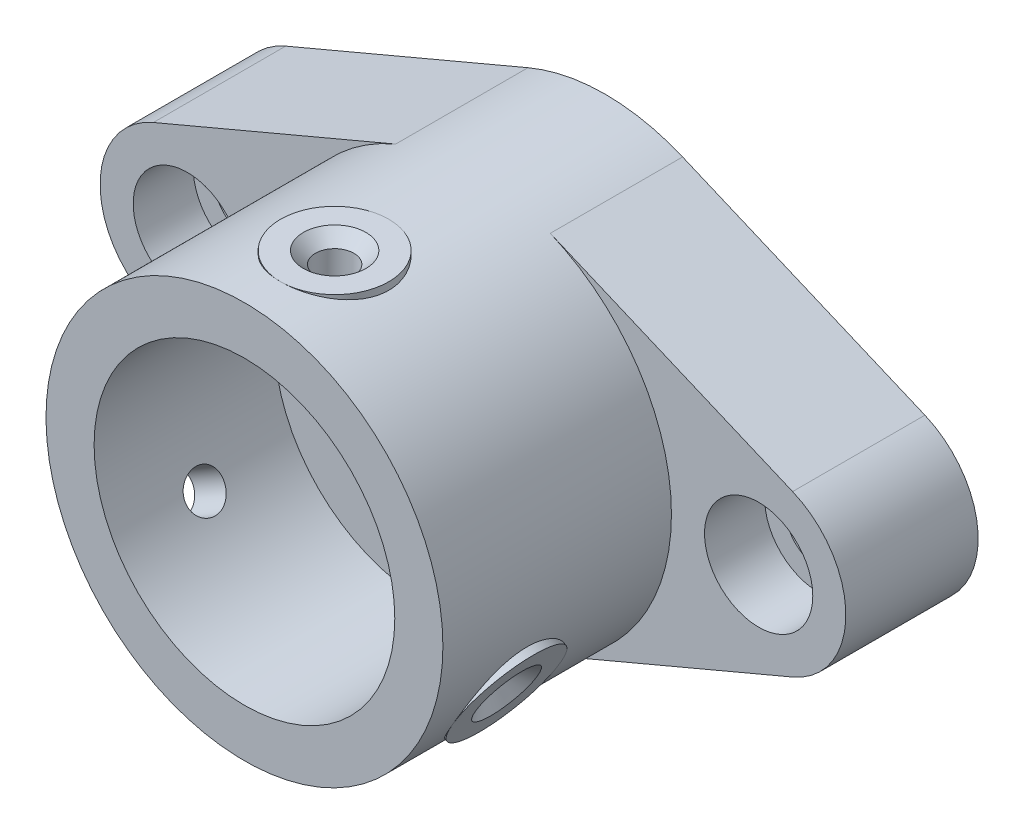
SolidWorks part; units mm, degrees
ref_plane "Front Plane" through (0, 0, 0) normal (0, 0, 1) x (1, 0, 0)
ref_plane "Top Plane" through (0, 0, 0) normal (0, 1, 0) x (1, 0, 0)
ref_plane "Right Plane" through (0, 0, 0) normal (1, 0, 0) x (0, 0, -1)
sketch "Sketch1" plane through (0, 0, 0) normal (0, 0, 1) x (1, 0, 0)
  circle A0 centre (0, 0) radius 12.5
  circle A1 centre (0, 0) radius 16.5
  dimension "D1" = 25
  dimension "D2" = 4
extrude "Boss-Extrude1" add sketch "Sketch1" along normal blind 15
sketch "Sketch2" plane through (0, 0, 0) normal (0, 0, -1) x (-1, 0, 0)
  circle A0 centre (0, 0) radius 16.5
  circle A1 centre (0, 0) radius 16.5 construction
extrude "Boss-Extrude2" add sketch "Sketch2" along normal blind 15
ref_plane "Plane1" through (0, 16.5, 0) normal (0, 1, 0) x (1, 0, 0)
sketch "Sketch3" plane through (0, 16.5, 0) normal (0, 1, 0) x (1, 0, 0)
  line L0 (-16.5, -15) -> (16.5, -15) construction
  circle A0 centre (0, -7.5) radius 4.5
  dimension "D1" = 9
  dimension "D2" = 7.5
extrude "Boss-Extrude3" add sketch "Sketch3" against normal up to surface up to face at (16.5, 0, 15)
sketch "Sketch4" plane through (0, 16.5, 0) normal (0, 1, 0) x (1, 0, 0)
  line L0 (-16.5, -15) -> (16.5, -15) construction
  circle A0 centre (0, -7.5) radius 1.6
  point P5 (0, 0)
  point P6 (0, 0)
  dimension "D1" = 3.2
  dimension "D2" = 7.5
extrude "Cut-Extrude1" cut sketch "Sketch4" against normal up to surface (4 mm away) up to face at (12.5, 0, 15)
pattern_circular "CirPattern1" count 3 over 360 about axis through (0, 0, 15) along (0, 0, 1) of "Cut-Extrude1", "Boss-Extrude3"
chamfer "Chamfer1" distance 1 angle 45 3 edges at (-14.2894, -8.25, 9.1) (14.2894, -8.25, 9.1) (0, 16.5, 9.1)
sketch "Sketch5" plane through (0, 0, -15) normal (0, 0, -1) x (-1, 0, 0)
  line L0 (26.5737, 6.6775) -> (6.4263, 15.1971)
  line L1 (26.5737, -6.6775) -> (6.4263, -15.1971)
  line L2 (-6.4263, 15.1971) -> (-26.5737, 6.6775)
  line L3 (-6.4263, -15.1971) -> (-26.5737, -6.6775)
  circle A0 centre (23.75, 0) radius 2.75
  circle A1 centre (-23.75, 0) radius 2.75
  arc A2 (26.5737, -6.6775) -> (26.5737, 6.6775) centre (23.75, 0) ccw
  arc A3 (-26.5737, 6.6775) -> (-26.5737, -6.6775) centre (-23.75, 0) ccw
  circle A4 centre (0, 0) radius 16.5 construction
  circle A6 centre (0, 0) radius 16.5 construction
  circle A8 centre (0, 0) radius 16.5 construction
  arc A9 (6.4263, 15.1971) -> (-6.4263, 15.1971) centre (0, 0) ccw
  arc A10 (6.4263, -15.1971) -> (-6.4263, -15.1971) centre (0, 0) cw
  dimension "D3" = 5.5
  dimension "D1" = 23.75
  dimension "D2" = 23.75
extrude "Boss-Extrude4" add sketch "Sketch5" against normal blind 11
sketch "Sketch6" plane through (0, 0, -4) normal (0, 0, 1) x (1, 0, 0)
  circle A0 centre (-23.75, 0) radius 4.5
  circle A1 centre (23.75, 0) radius 4.5
  dimension "D1" = 9
extrude "Cut-Extrude2" cut sketch "Sketch6" against normal blind 5
